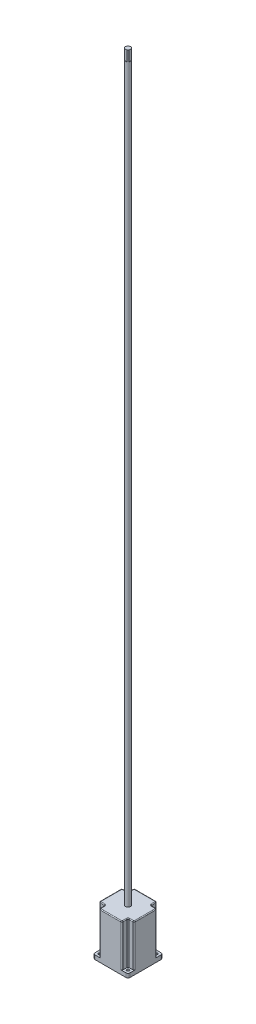
SolidWorks part; units mm, degrees
ref_plane "Спереди" through (0, 0, 0) normal (0, 0, 1) x (1, 0, 0)
ref_plane "Сверху" through (0, 0, 0) normal (0, 1, 0) x (1, 0, 0)
ref_plane "Справа" through (0, 0, 0) normal (1, 0, 0) x (0, 0, -1)
sketch "Эскиз1" plane through (0, 0, 0) normal (0, 1, 0) x (1, 0, 0)
  line L1 (-38, 43) -> (38, 43)
  line L2 (-43, 38) -> (-43, -38)
  line L3 (-38, -43) -> (38, -43)
  line L4 (43, 38) -> (43, -38)
  line L5 (-43, 43) -> (43, -43) construction
  line L6 (-43, -43) -> (43, 43) construction
  arc A1 (-38, 43) -> (-43, 38) centre (-38, 38) ccw
  arc A2 (38, 43) -> (43, 38) centre (38, 38) cw
  arc A3 (38, -43) -> (43, -38) centre (38, -38) ccw
  arc A4 (-43, -38) -> (-38, -43) centre (-38, -38) ccw
  point P0 (0, 0)
  dimension "D2" = 5
  dimension "D1" = 86
extrude "Бобышка-Вытянуть1" add sketch "Эскиз1" along normal blind 10
sketch "Эскиз2" plane through (0, 10, 0) normal (0, 1, 0) x (1, 0, 0)
  line L0 (-38, -43) -> (38, -43) construction
  line L1 (28, 43) -> (-28, 43)
  line L2 (43, 25) -> (43, -25)
  line L3 (25, -43) -> (-25, -43)
  line L4 (-43, 25) -> (-43, -25)
  line L5 (-43, 38) -> (-43, -38) construction
  line L6 (38, 43) -> (-38, 43) construction
  line L7 (43, -38) -> (43, 38) construction
  line L8 (28, -40) -> (28, -31)
  line L9 (31, -28) -> (40, -28)
  line L10 (0, 0) -> (0, 22.006) construction
  line L11 (0, 0) -> (23.6696, 0) construction
  line L12 (-31, -28) -> (-40, -28)
  line L13 (-28, -40) -> (-28, -31)
  line L14 (-28, 40) -> (-28, 31)
  line L15 (-31, 28) -> (-40, 28)
  line L16 (31, 28) -> (40, 28)
  line L17 (28, 40) -> (28, 31)
  line L18 (25, 43) -> (-25, 43)
  arc A0 (40, 28) -> (43, 25) centre (40, 25) cw
  arc A1 (31, 28) -> (28, 31) centre (31, 31) cw
  arc A2 (28, 40) -> (25, 43) centre (25, 40) ccw
  arc A3 (-28, 40) -> (-25, 43) centre (-25, 40) cw
  arc A4 (-28, 31) -> (-31, 28) centre (-31, 31) cw
  arc A5 (-40, 28) -> (-43, 25) centre (-40, 25) ccw
  arc A6 (-40, -28) -> (-43, -25) centre (-40, -25) cw
  arc A7 (-28, -40) -> (-25, -43) centre (-25, -40) ccw
  arc A8 (-31, -28) -> (-28, -31) centre (-31, -31) cw
  arc A9 (40, -28) -> (43, -25) centre (40, -25) ccw
  arc A10 (28, -40) -> (25, -43) centre (25, -40) cw
  arc A11 (28, -31) -> (31, -28) centre (31, -31) cw
  point P0 (0, 0)
  point P27 (43, 28)
  point P30 (28, 28)
  point P39 (-28, 28)
  point P42 (-43, 28)
  point P45 (-43, -28)
  point P48 (-28, -43)
  point P51 (-28, -28)
  point P54 (43, -28)
  point P57 (28, -43)
  point P60 (28, -28)
  line M12 (-43, 38) -> (-43, -38)
  line M14 (-38, -43) -> (38, -43)
  line M16 (43, -38) -> (43, 38)
  dimension "D2" = 3
  dimension "D1" = 15
extrude "Бобышка-Вытянуть2" add sketch "Эскиз2" along normal blind 104 contours L8 A11 L9 A9 A0 L16 A1 L17 A2 L1 A3 L14 A4 L15 A5 A6 L12 A8 L13 A7 A10 M16 M12 M14 region at (0, 10, 0)
sketch "Эскиз3" plane through (0, 0, 0) normal (0, -1, 0) x (1, 0, 0)
  circle A0 centre (0, 0) radius 36.5
  dimension "D1" = 73
extrude "Бобышка-Вытянуть3" add sketch "Эскиз3" along normal blind 2
sketch "Эскиз4" plane through (0, -2, 0) normal (0, -1, 0) x (1, 0, 0)
  circle A0 centre (0, 0) radius 6.35
  dimension "D1" = 12.7
extrude "Бобышка-Вытянуть4" add sketch "Эскиз4" along normal blind 35
sketch "Эскиз5" plane through (0, 114, 0) normal (0, 1, 0) x (1, 0, 0)
  circle A0 centre (0, 0) radius 6.35
  circle A1 centre (0, 0) radius 6.35 construction
extrude "Бобышка-Вытянуть5" add sketch "Эскиз5" along normal blind 1826.26
sketch "Эскиз6" plane through (0, -37, 0) normal (0, -1, 0) x (1, 0, 0)
  line L0 (-3.0854, 5.55) -> (5.55, 5.55)
  line L1 (5.55, 5.55) -> (5.55, -3.0854)
  line L2 (-3.0854, 5.55) -> (-3.0854, 7.6454)
  line L3 (-3.0854, 7.6454) -> (7.5315, 7.6454)
  line L4 (7.5315, 7.6454) -> (7.5315, -3.0854)
  line L5 (7.5315, -3.0854) -> (5.55, -3.0854)
  circle A0 centre (0, 0) radius 6.35 construction
  circle A1 centre (0, 0) radius 6.35 construction
  dimension "D1" = 11.9
  dimension "D2" = 11.9
extrude "Вырез-Вытянуть1" cut sketch "Эскиз6" against normal blind 25
sketch "Эскиз7" plane through (0, 1940.26, 0) normal (0, 1, 0) x (1, 0, 0)
  line L0 (-3.0854, -5.55) -> (5.55, -5.55)
  line L1 (5.55, -5.55) -> (5.55, 3.0854)
  line L2 (5.55, -3.0854) -> (5.55, 3.0854) construction
  line L4 (-3.0854, -5.55) -> (3.0854, -5.55) construction
  line L5 (5.55, 3.0854) -> (8.904, 3.0854)
  line L6 (8.904, 3.0854) -> (8.904, -8.9268)
  line L7 (8.904, -8.9268) -> (-3.0854, -8.9268)
  line L8 (-3.0854, -8.9268) -> (-3.0854, -5.55)
  circle A0 centre (0, 0) radius 6.35 construction
extrude "Вырез-Вытянуть2" cut sketch "Эскиз7" against normal blind 25
fillet "Скругление1" radius 2 24 edges at (-27.1213, 114, 42.1213) (-28, 114, 35.5) (-28.8787, 114, 28.8787) (-35.5, 114, 28) (-42.1213, 114, 27.1213) (-43, 114, 0) (-42.1213, 114, -27.1213) (-35.5, 114, -28) (-28.8787, 114, -28.8787) (-28, 114, -35.5) (-27.1213, 114, -42.1213) (0, 114, -43) (27.1213, 114, -42.1213) (28, 114, -35.5) (28.8787, 114, -28.8787) (35.5, 114, -28) (42.1213, 114, -27.1213) (43, 114, 0) (42.1213, 114, 27.1213) (35.5, 114, 28) (28.8787, 114, 28.8787) (28, 114, 35.5) (27.1213, 114, 42.1213) (0, 114, 43)
hole_wizard "Отверстие с зазором M61" positions "Эскиз8" profile "Эскиз9" hole size "M6" standard "GOST" end condition up to next
sketch "Эскиз8" plane through (0, 0, 0) normal (0, -1, 0) x (-1, 0, 0)
  line L0 (0, 0) -> (0, -28.1171) construction
  line L2 (0, 0) -> (29.6951, 0) construction
  point P0 (34.8, -34.8)
  point P14 (-34.8, -34.8)
  point P16 (-34.8, 34.8)
  point P17 (34.8, 34.8)
  dimension "D1" = 69.6
  dimension "D2" = 69.6
sketch "Эскиз9" plane through (-34.8, 0, 34.8) normal (1, 0, 0) x (0, 0, -1)
  line L0 (0, 0) -> (0, 10)
  line L1 (0, 10) -> (3.25, 10)
  line L2 (3.25, 10) -> (3.25, 0)
  line L5 (3.25, 0) -> (0, 0)
  line L11 (0, -6.35) -> (0, 107.95) construction
  dimension "Диаметр сквозного отверстия" = 6.5
  dimension "Глубина сквозного отверстия" = 10
sketch "Эскиз10" plane through (0, 0, -43) normal (0, 0, -1) x (-1, 0, 0)
  circle A0 centre (0, 100.9179) radius 6
  dimension "D1" = 12
extrude "Бобышка-Вытянуть6" add sketch "Эскиз10" along normal blind 2
fillet "Скругление2" radius 1.5 1 edges at (-6, 100.9179, -45)
sketch "Эскиз11" plane through (0, 0, -45) normal (0, 0, -1) x (-1, 0, 0)
  circle A0 centre (0, 100.9179) radius 2.2224
extrude "Бобышка-Вытянуть7" add sketch "Эскиз11" along normal blind 5
scale "Scale1" scale about centroid uniform scaling yes scale factor 5
